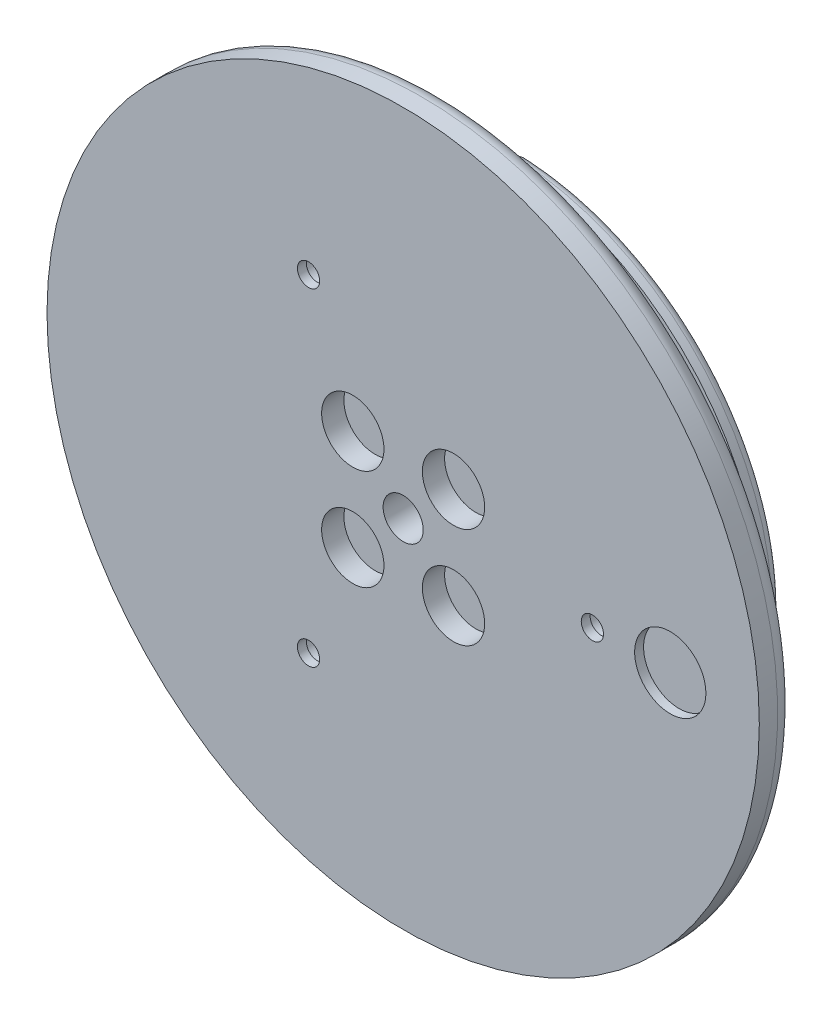
SolidWorks part; units mm, degrees
other "Main Coupler Piece"
other "insert3"
other "insert2"
other "insert1"
other "back piece"
ref_plane "Front Plane" through (0, 0, 0) normal (0, 0, 1) x (1, 0, 0)
ref_plane "Top Plane" through (0, 0, 0) normal (0, 1, 0) x (1, 0, 0)
ref_plane "Right Plane" through (0, 0, 0) normal (1, 0, 0) x (0, 0, -1)
sketch "Sketch1" plane through (0, 0, 0) normal (0, 0, 1) x (1, 0, 0)
  circle A0 centre (0, 0) radius 12.5
  circle A1 centre (0, 0) radius 30
  dimension "D1" = 25
  dimension "D2" = 60
extrude "Boss-Extrude1" add sketch "Sketch1" along normal blind 6
sketch "Sketch2" plane through (0, 0, 6) normal (0, 0, 1) x (1, 0, 0)
  line L1 (-5.656, 5.6577) -> (5.656, 5.6577) construction
  line L2 (-5.656, 5.6577) -> (-5.656, -5.6577) construction
  line L3 (-5.656, -5.6577) -> (5.656, -5.6577) construction
  line L4 (5.656, 5.6577) -> (5.656, -5.6577) construction
  circle A0 centre (0, 0) radius 2.25
  circle A1 centre (-5.656, 5.6577) radius 1.5
  circle A2 centre (-5.656, -5.6577) radius 1.5
  circle A3 centre (5.656, -5.6577) radius 1.5
  circle A4 centre (5.656, 5.6577) radius 1.5
  circle A5 centre (0, 0) radius 40
  point P15 (0, -5.6577)
  point P16 (-5.656, 0)
  dimension "D1" = 4.5
  dimension "D4" = 3
  dimension "D5" = 80
  dimension "D2" = 16
  dimension "D3" = 11.3154
extrude "Boss-Extrude2" add sketch "Sketch2" along normal blind 4
sketch "Sketch3" plane through (0, 0, 10) normal (0, 0, 1) x (1, 0, 0)
  circle A0 centre (-5.656, 5.6577) radius 3.5
  circle A1 centre (5.656, 5.6577) radius 3.5
  circle A2 centre (5.656, -5.6577) radius 3.5
  circle A3 centre (-5.656, -5.6577) radius 3.5
  dimension "D1" = 7
extrude "Cut-Extrude1" cut sketch "Sketch3" against normal blind 2.5
sketch "Sketch4" plane through (0, 0, 0) normal (0, 0, -1) x (-1, 0, 0)
  circle A0 centre (-20, 0) radius 5.15
  circle A1 centre (0, -20) radius 5.15
  circle A2 centre (0, 0) radius 20 construction
  circle A3 centre (0, 0) radius 20 construction
  circle A4 centre (20, 0) radius 5.15
  circle A5 centre (0, 0) radius 20 construction
  circle A6 centre (0, 20) radius 5.15
  circle A7 centre (0, 0) radius 20 construction
  circle A8 centre (0, 20) radius 2.65 construction
  circle A9 centre (14.1421, 14.1421) radius 2.65
  circle A10 centre (0, 0) radius 20 construction
  circle A11 centre (20, 0) radius 2.65 construction
  circle A12 centre (0, 0) radius 20 construction
  circle A13 centre (14.1421, -14.1421) radius 2.65
  circle A14 centre (0, 0) radius 20 construction
  circle A15 centre (0, -20) radius 2.65 construction
  circle A16 centre (0, 0) radius 20 construction
  circle A17 centre (-14.1421, -14.1421) radius 2.65
  circle A18 centre (0, 0) radius 20 construction
  circle A19 centre (-20, 0) radius 2.65 construction
  circle A20 centre (0, 0) radius 20 construction
  circle A21 centre (-14.1421, 14.1421) radius 2.65
  circle A22 centre (0, 0) radius 20 construction
  point P17 (0, 0)
  point P39 (0, 0)
  dimension "D1" = 10.3
  dimension "D2" = 40
  dimension "D4" = 5.3
  dimension "D3" = 4
  dimension "D5" = 8
extrude "Cut-Extrude2" cut sketch "Sketch4" against normal blind 3 contours A4
sketch "Sketch5" plane through (0, 0, 7.5) normal (0, 0, 1) x (1, 0, 0)
  circle A0 centre (-5.656, 5.6577) radius 3.5
  circle A1 centre (5.656, 5.6577) radius 3.5
  circle A2 centre (-5.656, -5.6577) radius 3.5
  circle A3 centre (5.656, -5.6577) radius 3.5
extrude "Boss-Extrude3" add sketch "Sketch5" against normal blind 0.2
sketch "Sketch6" plane through (0, 0, 0) normal (0, 0, -1) x (-1, 0, 0)
  circle A0 centre (-21.25, 0) radius 1.25
  circle A1 centre (0, 0) radius 12.5 construction
  circle A2 centre (10.625, 18.403) radius 1.25
  circle A3 centre (10.625, -18.403) radius 1.25
  circle A4 centre (0, 0) radius 30 construction
  circle A5 centre (-34.2276, 0) radius 2.5 construction
  point P7 (0, 0)
  point P12 (0, 0)
  dimension "D1" = 21.25
  dimension "D2" = 2.5
  dimension "D4" = 5
  dimension "D3" = 3
extrude "Cut-Extrude3" cut sketch "Sketch6" against normal blind 10
sketch "Sketch7" plane through (0, 0, 0) normal (0, 0, -1) x (-1, 0, 0)
  circle A0 centre (-21.25, 0) radius 3.125
  circle A1 centre (10.625, 18.403) radius 3.125
  circle A2 centre (10.625, -18.403) radius 3.125
  dimension "D1" = 6.25
extrude "Cut-Extrude4" cut sketch "Sketch7" against normal offset from surface (9 mm away) 1 up to face at (20, 0, 10)
sketch "Sketch8" plane through (0, 0, 0) normal (0, 0, -1) x (-1, 0, 0)
  circle A0 centre (20, 0) radius 2
  circle A1 centre (20, 0) radius 5.15 construction
  circle A2 centre (-10, -17.3205) radius 2
  circle A3 centre (-10, 17.3205) radius 2
  circle A4 centre (0, 0) radius 30 construction
  circle A5 centre (17.3205, -10) radius 2
  circle A6 centre (10, -17.3205) radius 2
  circle A7 centre (0, -20) radius 2
  circle A8 centre (-10, -17.3205) radius 2
  circle A9 centre (-17.3205, -10) radius 2
  circle A10 centre (-20, 0) radius 2
  circle A11 centre (-17.3205, 10) radius 2
  circle A12 centre (-10, 17.3205) radius 2
  circle A13 centre (0, 20) radius 2
  circle A14 centre (10, 17.3205) radius 2
  circle A15 centre (17.3205, 10) radius 2
  circle A16 centre (0, 0) radius 30 construction
  point P11 (0, 0)
  point P36 (0, 0)
  dimension "D1" = 4
  dimension "D2" = 3
  dimension "D3" = 12
extrude "Cut-Extrude5" cut sketch "Sketch8" against normal offset from surface (8 mm away) 2 contours A11 | A9 | A15 | A5 | A13 | A7 | A3 | A2 up to face at (20, 0, 10)
sketch "Sketch9" plane through (0, 0, 0) normal (0, 0, -1) x (-1, 0, 0)
  circle A0 centre (-21.25, 0) radius 3
  circle A1 centre (10.625, 18.403) radius 3
  circle A2 centre (10.625, -18.403) radius 3
  dimension "D1" = 6
extrude "Boss-Extrude4" add sketch "Sketch9" along normal blind 0.5 separate body
sketch "Sketch10" plane through (0, 0, -0.5) normal (0, 0, -1) x (-1, 0, 0)
  circle A0 centre (20, 0) radius 5.15
  circle A5 centre (-10, 17.3205) radius 2
  circle A6 centre (-10, -17.3205) radius 2
  circle A7 centre (20, 0) radius 5.15 construction
  circle A8 centre (-17.3205, 10) radius 2
  circle A9 centre (0, 20) radius 2
  circle A10 centre (17.3205, 10) radius 2
  circle A11 centre (17.3205, -10) radius 2
  circle A12 centre (0, -20) radius 2
  circle A13 centre (-17.3205, -10) radius 2
  circle A16 centre (20, 0) radius 5.15
  circle A17 centre (0, 0) radius 30
  circle A18 centre (0, 0) radius 12.5
  circle A19 centre (20, 0) radius 5.15
  circle A22 centre (-10, -17.3205) radius 2 construction
  circle A23 centre (-10, 17.3205) radius 2 construction
  point P13 (0, 0)
  point P14 (-9.2127, -22.405)
  circle M3 centre (10.625, 18.403) radius 3
sketch "Sketch11" plane through (0, 0, 9) normal (0, 0, -1) x (-1, 0, 0)
  circle A0 centre (-21.25, 0) radius 3
  circle A1 centre (10.625, 18.403) radius 3
  circle A2 centre (10.625, -18.403) radius 3
  circle A4 centre (-21.25, 0) radius 1.5
  circle A5 centre (10.625, 18.403) radius 1.5
  circle A6 centre (10.625, -18.403) radius 1.5
  dimension "D1" = 6
  dimension "D2" = 3
extrude "Boss-Extrude6" add sketch "Sketch11" along normal blind 3 separate body
extrude "Boss-Extrude7" add sketch "Sketch10" along normal blind 1.2 separate body contours A17 A18 A0 A8 A9 A10 A11 A12 A13 M3 | M3
delete or keep bodies "Body-Delete/Keep 1" type delete bodies bodies 111
delete or keep bodies "Body-Delete/Keep 2" type delete bodies bodies 110
delete or keep bodies "Body-Delete/Keep 3" type delete bodies bodies 109
fillet "Fillet1" radius 10 1 edges at (30, 0, 6)
fillet "Fillet2" radius 2 1 edges at (40, 0, 6)
sketch "Sketch12" plane through (0, 0, 6) normal (0, 0, -1) x (-1, 0, 0)
  circle A0 centre (0, 0) radius 12.5
  circle A1 centre (0, 0) radius 2.25
  circle A2 centre (-5.656, 5.6577) radius 1.5
  circle A3 centre (5.656, 5.6577) radius 1.5
  circle A4 centre (5.656, -5.6577) radius 1.5
  circle A5 centre (-5.656, -5.6577) radius 1.5
extrude "Boss-Extrude8" add sketch "Sketch12" along normal blind 2
sketch "Sketch14" plane through (0, 0, 10) normal (0, 0, 1) x (1, 0, 0)
  circle A0 centre (30, 0) radius 4
  point P2 (0, 0)
  dimension "D1" = 8
  dimension "D2" = 30
extrude "Cut-Extrude6" cut sketch "Sketch14" against normal blind 1
sketch "Sketch15" plane through (0, 0, -1.7) normal (0, 0, -1) x (-1, 0, 0)
  line L0 (0, 0) -> (-28, 0) construction
  line L1 (-27.9821, 1) -> (-12.4599, 1)
  line L2 (-27.9821, -1) -> (-12.4599, -1)
  line L3 (14.8571, 23.7332) -> (7.096, 10.2906)
  line L4 (13.125, 24.7332) -> (5.3639, 11.2906)
  line L5 (13.125, -24.7332) -> (5.3639, -11.2906)
  line L6 (14.8571, -23.7332) -> (7.096, -10.2906)
  circle A0 centre (0, 0) radius 28
  circle A1 centre (0, 0) radius 30
  circle A2 centre (0, 0) radius 30 construction
  circle A3 centre (0, 0) radius 12.5 construction
  circle A4 centre (0, 0) radius 12.5
  circle A5 centre (0, 0) radius 12.5 construction
  point P27 (0, 0)
  circle M7 centre (0, 0) radius 12.5
  circle M17 centre (0, 0) radius 30
  dimension "D1" = 2
  dimension "D2" = 1
  dimension "D3" = 1
  dimension "D4" = 3
extrude "Boss-Extrude10" add sketch "Sketch15" along normal blind 0.75 contours A0 M17 | L3 A0 L4 M7 | L5 A0 L6 M7 | L0 A0 L2 M7 | L0 A4 L1 A0
fillet "Fillet3" radius 10 9 edges at (-9.2445, -18.0119, -1.7) (-28, 0, -1.7) (-9.2445, 18.0119, -1.7) (20.221, -1, -1.7) (-10.9765, -17.0119, -1.7) (14, -24.2487, -1.7) (-10.9765, 17.0119, -1.7) (20.221, 1, -1.7) (14, 24.2487, -1.7)
fillet "Fillet4" radius 4 9 edges at (-9.2445, 18.0119, -2.45) (-10.9765, 17.0119, -2.45) (-28, 0, -2.45) (-10.9765, -17.0119, -2.45) (-9.2445, -18.0119, -2.45) (14, -24.2487, -2.45) (20.221, -1, -2.45) (20.221, 1, -2.45) (14, 24.2487, -2.45)
fillet "Fillet5" radius 1 1 edges at (-30, 0, -2.45)
